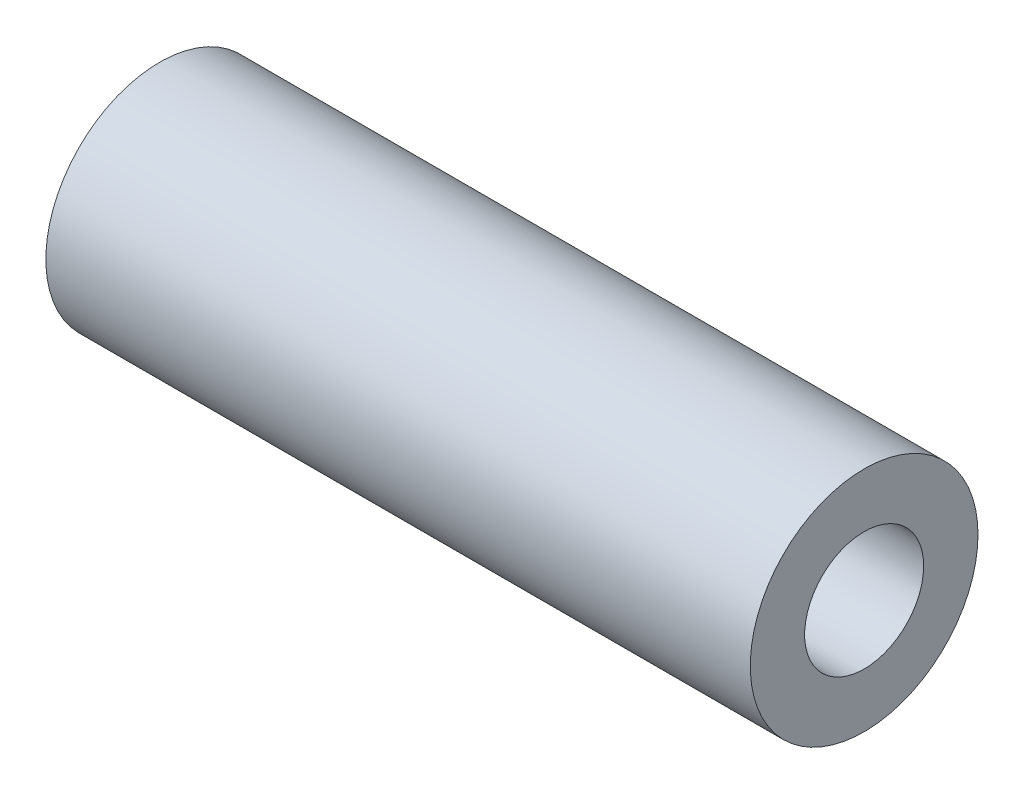
SolidWorks part; units mm, degrees
material "6061-T6 (SS)"
ref_plane "Front Plane" through (0, 0, 0) normal (0, 0, 1) x (1, 0, 0)
ref_plane "Top Plane" through (0, 0, 0) normal (0, 1, 0) x (1, 0, 0)
ref_plane "Right Plane" through (0, 0, 0) normal (1, 0, 0) x (0, 0, -1)
sketch "Sketch1" plane through (0, 0, 0) normal (1, 0, 0) x (0, 0, -1)
  circle A0 centre (0, 0) radius 4.7625
  circle A1 centre (0, 0) radius 2.4892
  dimension "D1" = 4.9784
  dimension "D2" = 9.525
extrude "Boss-Extrude1" add sketch "Sketch1" along normal mid plane 29.464
